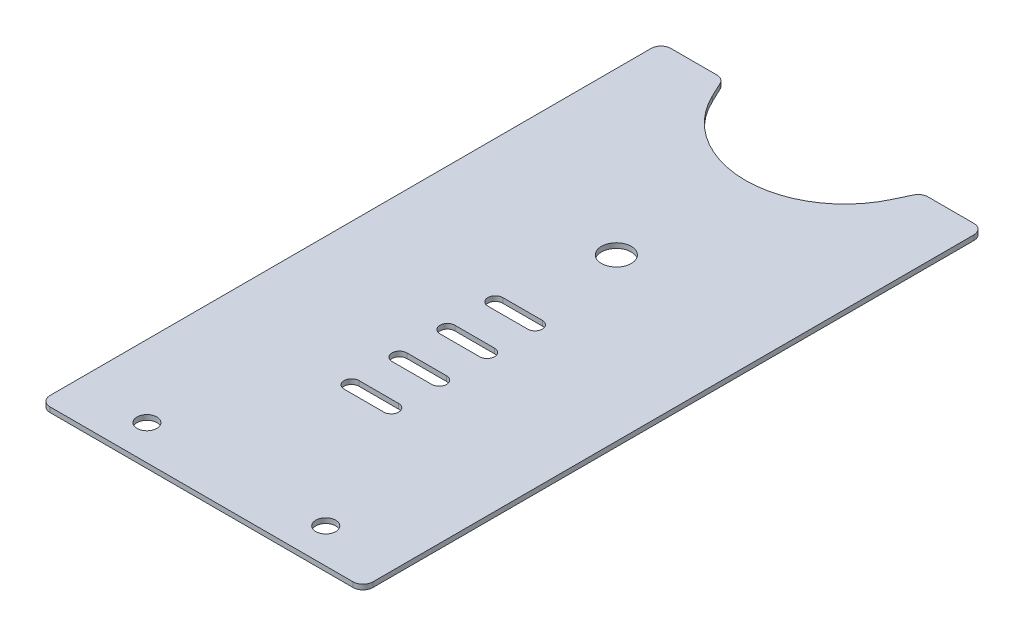
SolidWorks part; units mm, degrees
material "C-玻璃纤维"
ref_plane "前视基准面" through (0, 0, 0) normal (0, 0, 1) x (1, 0, 0)
ref_plane "上视基准面" through (0, 0, 0) normal (0, 1, 0) x (1, 0, 0)
ref_plane "右视基准面" through (0, 0, 0) normal (1, 0, 0) x (0, 0, -1)
sketch "草图1" plane through (0, 0, 0) normal (0, 1, 0) x (1, 0, 0)
  line L0 (0, -55) -> (0, 55) construction
  line L1 (-18.0726, 120.9337) -> (-20, 125)
  line L2 (-20, 125) -> (-32.5, 125)
  line L3 (-32.5, 125) -> (-32.5, 0)
  line L4 (-32.5, 0) -> (32.5, 0)
  line L5 (32.5, 125) -> (32.5, 0)
  line L6 (20, 125) -> (32.5, 125)
  line L7 (18.0726, 120.9337) -> (20, 125)
  line L29 (-4, 34.1906) -> (4, 34.1906) construction
  line L30 (-4, 35.6906) -> (4, 35.6906)
  line L31 (-4, 32.6906) -> (4, 32.6906)
  line L32 (-4, 43.8406) -> (4, 43.8406) construction
  line L33 (-4, 45.3406) -> (4, 45.3406)
  line L34 (-4, 42.3406) -> (4, 42.3406)
  line L35 (-4, 53.4906) -> (4, 53.4906) construction
  line L36 (-4, 54.9906) -> (4, 54.9906)
  line L37 (-4, 51.9906) -> (4, 51.9906)
  line L38 (-4, 63.1406) -> (4, 63.1406) construction
  line L39 (-4, 64.6406) -> (4, 64.6406)
  line L40 (-4, 61.6406) -> (4, 61.6406)
  arc A1 (-18.0726, 120.9337) -> (18.0726, 120.9337) centre (0, 129.5) ccw
  circle A7 centre (-18, 7) radius 2
  circle A8 centre (18, 7) radius 2
  circle A22 centre (0, 83.51) radius 3
  arc A23 (-4, 35.6906) -> (-4, 32.6906) centre (-4, 34.1906) ccw
  arc A24 (4, 32.6906) -> (4, 35.6906) centre (4, 34.1906) ccw
  arc A25 (-4, 45.3406) -> (-4, 42.3406) centre (-4, 43.8406) ccw
  arc A26 (4, 42.3406) -> (4, 45.3406) centre (4, 43.8406) ccw
  arc A27 (-4, 54.9906) -> (-4, 51.9906) centre (-4, 53.4906) ccw
  arc A28 (4, 51.9906) -> (4, 54.9906) centre (4, 53.4906) ccw
  arc A29 (-4, 64.6406) -> (-4, 61.6406) centre (-4, 63.1406) ccw
  arc A30 (4, 61.6406) -> (4, 64.6406) centre (4, 63.1406) ccw
  point P0 (0, 34.1906)
  point P2 (-3.942, 63.1406)
  point P5 (-3.94, 43.8406)
  point P11 (0, 43.8406)
  point P15 (0, 0)
  point P28 (0.05, 83.51)
  point P46 (0, 53.4906)
  point P59 (0, 63.1406)
  dimension "D1" = 7
  dimension "D2" = 12.5
  dimension "D3" = 125
  dimension "D5" = 36
  dimension "D7" = 20
  dimension "D8" = 4
  dimension "D14" = 20.3694
  dimension "D15" = 6
  dimension "D4" = 65
  dimension "D6" = 4.5
  dimension "D9" = 3
  dimension "D10" = 8
  dimension "D11" = 34.1906
  dimension "D13" = 9.65
  dimension "D12" = 4
extrude "凸台-拉伸1" add sketch "草图1" along normal blind 1
fillet "圆角1" radius 2 6 edges at (20, 0.5, -125) (32.5, 0.5, -125) (-20, 0.5, -125) (-32.5, 0.5, 0) (-32.5, 0.5, -125) (32.5, 0.5, 0)
sketch "草图2" plane through (0, 1, 0) normal (0, 1, 0) x (1, 0, 0)
  line L0 (173.3429, 629.6393) -> (1026.6763, 629.6393) construction
  line L1 (0, -55) -> (0, 55) construction
  line L2 (-32.5, 123) -> (-32.5, 2) construction
  line L3 (178.2638, 678.6709) -> (1031.5971, 678.6709) construction
  line L4 (-2.075, 106.1092) -> (-3.3584, 101.7889)
  line L5 (-3.3584, 101.7889) -> (3.3584, 101.7889)
  line L6 (-19.8675, 109.6697) -> (-10.4108, 107.827)
  line L7 (-22.3294, 102.162) -> (-12.7506, 101.6071)
  line L8 (-3.1133, 105.1582) -> (-4.1841, 101.0074)
  line L9 (-4.1841, 101.0074) -> (4.1841, 101.0074)
  line L10 (-3.9935, 81.2053) -> (-5.2494, 75.9189)
  line L11 (-5.2494, 75.9189) -> (-0.0463, 74.6829)
  line L12 (22.3294, 102.162) -> (12.7506, 101.6071)
  line L13 (5.2494, 75.9189) -> (-0.0463, 74.6829)
  line L14 (3.9935, 81.2053) -> (5.2494, 75.9189)
  line L15 (3.1133, 105.1582) -> (4.1841, 101.0074)
  line L16 (19.8675, 109.6697) -> (10.4108, 107.827)
  line L17 (-3.3318, 87.2118) -> (-4.3462, 82.5327)
  line L18 (-4.3462, 82.5327) -> (0.3515, 81.5143)
  line L19 (-2.9266, 92.7641) -> (-4.3552, 87.9155)
  line L20 (-4.3552, 87.9155) -> (-0.0345, 87.0586)
  line L21 (-2.7511, 98.0204) -> (-3.8827, 93.8409)
  line L22 (-3.8827, 93.8409) -> (-0.0463, 93.2555)
  line L23 (3.8827, 93.8409) -> (-0.0463, 93.2555)
  line L24 (2.7511, 98.0204) -> (3.8827, 93.8409)
  line L25 (4.3462, 82.5327) -> (0.3515, 81.5143)
  line L26 (3.3318, 87.2118) -> (4.3462, 82.5327)
  line L27 (4.3552, 87.9155) -> (-0.0345, 87.0586)
  line L28 (2.9266, 92.7641) -> (4.3552, 87.9155)
  line L29 (2.075, 106.1092) -> (3.3584, 101.7889)
  line L30 (-32.5, 100) -> (32.5, 100) construction
  line L32 (32.5, 2) -> (32.5, 123) construction
  line L33 (-2.075, 46.1092) -> (-3.3584, 41.7889)
  line L34 (-21.2653, 125) -> (-30.5, 125) construction
  line L35 (-3.3584, 41.7889) -> (3.3584, 41.7889)
  line L38 (0.5283, 100) -> (-0.4837, 100) construction
  line L43 (-19.8675, 49.6697) -> (-10.4108, 47.827)
  line L45 (-22.3294, 42.162) -> (-12.7506, 41.6071)
  line L60 (-3.1133, 45.1582) -> (-4.1841, 41.0074)
  line L61 (-4.1841, 41.0074) -> (4.1841, 41.0074)
  line L62 (-3.9935, 21.2053) -> (-5.2494, 15.9189)
  line L63 (-5.2494, 15.9189) -> (-0.0463, 14.6829)
  line L64 (22.3294, 42.162) -> (12.7506, 41.6071)
  line L65 (5.2494, 15.9189) -> (-0.0463, 14.6829)
  line L66 (3.9935, 21.2053) -> (5.2494, 15.9189)
  line L67 (3.1133, 45.1582) -> (4.1841, 41.0074)
  line L68 (19.8675, 49.6697) -> (10.4108, 47.827)
  line L69 (-3.3318, 27.2118) -> (-4.3462, 22.5327)
  line L70 (-4.3462, 22.5327) -> (0.3515, 21.5143)
  line L71 (-2.9266, 32.7641) -> (-4.3552, 27.9155)
  line L72 (-4.3552, 27.9155) -> (-0.0345, 27.0586)
  line L73 (-2.7511, 38.0204) -> (-3.8827, 33.8409)
  line L74 (-3.8827, 33.8409) -> (-0.0463, 33.2555)
  line L75 (3.8827, 33.8409) -> (-0.0463, 33.2555)
  line L76 (2.7511, 38.0204) -> (3.8827, 33.8409)
  line L77 (4.3462, 22.5327) -> (0.3515, 21.5143)
  line L78 (3.3318, 27.2118) -> (4.3462, 22.5327)
  line L79 (4.3552, 27.9155) -> (-0.0345, 27.0586)
  line L80 (2.9266, 32.7641) -> (4.3552, 27.9155)
  line L81 (2.075, 46.1092) -> (3.3584, 41.7889)
  spline S0 degree 3 poles (-16.5617, 116.7497) (-9.7804, 114.7297) (-9.7818, 114.8748) (-2.075, 114.348) knots 0 0 0 0 1 1 1 1
  spline S1 degree 3 poles (-2.075, 114.348) (-0.8509, 119.3678) (-0.3777, 81.7523) (1.5803, 116.7571) (2.075, 114.348) knots 0 0 0 0 0.430189 1 1 1 1
  spline S2 degree 3 poles (-16.5617, 116.7497) (-16.4279, 113.773) (-14.3476, 111.5589) (-11.6385, 111.1576) knots 0 0 0 0 1 1 1 1
  spline S3 degree 3 poles (-11.6385, 111.1576) (-11.3827, 108.4756) (-8.8629, 107.6259) (-6.7601, 107.827) knots 0 0 0 0 1 1 1 1
  spline S4 degree 3 poles (-6.7601, 107.827) (-6.04, 106.3521) (-5.0028, 105.2891) (-2.075, 106.1092) knots 0 0 0 0 1 1 1 1
  spline S5 degree 3 poles (6.7601, 107.827) (6.04, 106.3521) (5.0028, 105.2891) (2.075, 106.1092) knots 0 0 0 0 1 1 1 1
  spline S6 degree 3 poles (11.6385, 111.1576) (11.3827, 108.4756) (8.8629, 107.6259) (6.7601, 107.827) knots 0 0 0 0 1 1 1 1
  spline S7 degree 3 poles (16.5617, 116.7497) (16.4279, 113.773) (14.3476, 111.5589) (11.6385, 111.1576) knots 0 0 0 0 1 1 1 1
  spline S8 degree 3 poles (16.5617, 116.7497) (9.7804, 114.7297) (9.7818, 114.8748) (2.075, 114.348) knots 0 0 0 0 1 1 1 1
  spline S9 degree 3 poles (-19.8675, 109.6697) (-17.8911, 104.7559) (-10.8375, 98.5637) (-2.7511, 98.0204) knots 0 0 0 0 1 1 1 1
  spline S10 degree 3 poles (-22.3294, 102.162) (-18.2675, 95.7927) (-11.2844, 93.146) (-2.9266, 92.7641) knots 0 0 0 0 1 1 1 1
  spline S11 degree 3 poles (-25.3767, 95.6389) (-23.0081, 91.1831) (-15.2931, 88.1635) (-3.3318, 87.2118) knots 0 0 0 0 1 1 1 1
  spline S12 degree 3 poles (-27.9693, 89.3013) (-24.3699, 84.7234) (-28.8455, 85.1687) (-3.9935, 81.2053) knots 0 0 0 0 1 1 1 1
  spline S13 degree 3 poles (-27.9693, 89.3013) (-24.7439, 88.2361) (-23.7856, 87.9656) (-11.4548, 88.2965) knots 0 0 0 0 1 1 1 1
  spline S14 degree 3 poles (-25.3767, 95.6389) (-22.4978, 95.0398) (-19.9992, 94.9933) (-14.7163, 95.4427) knots 0 0 0 0 1 1 1 1
  spline S15 degree 3 poles (-10.4108, 107.827) (-9.3209, 107.1792) (-9.1946, 107.0534) (-7.2518, 107.0534) knots 0 0 0 0 1 1 1 1
  spline S16 degree 3 poles (-7.2518, 107.0534) (-6.1832, 105.4019) (-5.1373, 104.9889) (-3.1133, 105.1582) knots 0 0 0 0 1 1 1 1
  spline S17 degree 3 poles (25.3767, 95.6389) (22.4978, 95.0398) (19.9992, 94.9933) (14.7163, 95.4427) knots 0 0 0 0 1 1 1 1
  spline S18 degree 3 poles (27.9693, 89.3013) (24.7439, 88.2361) (23.7856, 87.9656) (11.4548, 88.2965) knots 0 0 0 0 1 1 1 1
  spline S19 degree 3 poles (27.9693, 89.3013) (24.3699, 84.7234) (28.8455, 85.1687) (3.9935, 81.2053) knots 0 0 0 0 1 1 1 1
  spline S20 degree 3 poles (25.3767, 95.6389) (23.0081, 91.1831) (15.2931, 88.1635) (3.3318, 87.2118) knots 0 0 0 0 1 1 1 1
  spline S21 degree 3 poles (22.3294, 102.162) (18.2675, 95.7927) (11.2844, 93.146) (2.9266, 92.7641) knots 0 0 0 0 1 1 1 1
  spline S22 degree 3 poles (19.8675, 109.6697) (17.8911, 104.7559) (10.8375, 98.5637) (2.7511, 98.0204) knots 0 0 0 0 1 1 1 1
  spline S23 degree 3 poles (7.2518, 107.0534) (6.1832, 105.4019) (5.1373, 104.9889) (3.1133, 105.1582) knots 0 0 0 0 1 1 1 1
  spline S24 degree 3 poles (10.4108, 107.827) (9.3209, 107.1792) (9.1946, 107.0534) (7.2518, 107.0534) knots 0 0 0 0 1 1 1 1
  spline S25 degree 3 poles (-16.5617, 56.7497) (-9.7804, 54.7297) (-9.7818, 54.8751) (-2.075, 54.3482) knots 0 0 0 0 1 1 1 1
  spline S26 degree 3 poles (-2.075, 54.3482) (-0.8509, 59.368) (-0.3777, 60.539) (1.5803, 59.5765) (2.075, 54.3482) knots 0 0 0 0 0.430189 1 1 1 1
  spline S27 degree 3 poles (-16.5617, 56.7497) (-16.4279, 53.773) (-14.3476, 51.5589) (-11.6385, 51.1576) knots 0 0 0 0 1 1 1 1
  spline S28 degree 3 poles (-11.6385, 51.1576) (-11.3827, 48.4756) (-8.8629, 47.6259) (-6.7601, 47.827) knots 0 0 0 0 1 1 1 1
  spline S29 degree 3 poles (-6.7601, 47.827) (-6.04, 46.3521) (-5.0028, 45.2891) (-2.075, 46.1092) knots 0 0 0 0 1 1 1 1
  spline S30 degree 3 poles (6.7601, 47.827) (6.04, 46.3521) (5.0028, 45.2891) (2.075, 46.1092) knots 0 0 0 0 1 1 1 1
  spline S31 degree 3 poles (11.6385, 51.1576) (11.3827, 48.4756) (8.8629, 47.6259) (6.7601, 47.827) knots 0 0 0 0 1 1 1 1
  spline S32 degree 3 poles (16.5617, 56.7497) (16.4279, 53.773) (14.3476, 51.5589) (11.6385, 51.1576) knots 0 0 0 0 1 1 1 1
  spline S33 degree 3 poles (16.5617, 56.7497) (9.7804, 54.7297) (9.7818, 54.8751) (2.075, 54.3482) knots 0 0 0 0 1 1 1 1
  spline S34 degree 3 poles (-19.8675, 49.6697) (-17.8911, 44.7559) (-10.8375, 38.5637) (-2.7511, 38.0204) knots 0 0 0 0 1 1 1 1
  spline S35 degree 3 poles (-22.3294, 42.162) (-18.2675, 35.7927) (-11.2844, 33.146) (-2.9266, 32.7641) knots 0 0 0 0 1 1 1 1
  spline S36 degree 3 poles (-25.3767, 35.6389) (-23.0081, 31.1831) (-15.2931, 28.1635) (-3.3318, 27.2118) knots 0 0 0 0 1 1 1 1
  spline S37 degree 3 poles (-27.9693, 29.3013) (-24.3699, 24.7234) (-28.8455, 25.1687) (-3.9935, 21.2053) knots 0 0 0 0 1 1 1 1
  spline S38 degree 3 poles (-27.9693, 29.3013) (-24.7439, 28.2361) (-23.7856, 27.9656) (-11.4548, 28.2965) knots 0 0 0 0 1 1 1 1
  spline S39 degree 3 poles (-25.3767, 35.6389) (-22.4978, 35.0398) (-19.9992, 34.9933) (-14.7163, 35.4427) knots 0 0 0 0 1 1 1 1
  spline S40 degree 3 poles (-10.4108, 47.827) (-9.3209, 47.1792) (-9.1946, 47.0534) (-7.2518, 47.0534) knots 0 0 0 0 1 1 1 1
  spline S41 degree 3 poles (-7.2518, 47.0534) (-6.1832, 45.4019) (-5.1373, 44.9889) (-3.1133, 45.1582) knots 0 0 0 0 1 1 1 1
  spline S42 degree 3 poles (25.3767, 35.6389) (22.4978, 35.0398) (19.9992, 34.9933) (14.7163, 35.4427) knots 0 0 0 0 1 1 1 1
  spline S43 degree 3 poles (27.9693, 29.3013) (24.7439, 28.2361) (23.7856, 27.9656) (11.4548, 28.2965) knots 0 0 0 0 1 1 1 1
  spline S44 degree 3 poles (27.9693, 29.3013) (24.3699, 24.7234) (28.8455, 25.1687) (3.9935, 21.2053) knots 0 0 0 0 1 1 1 1
  spline S45 degree 3 poles (25.3767, 35.6389) (23.0081, 31.1831) (15.2931, 28.1635) (3.3318, 27.2118) knots 0 0 0 0 1 1 1 1
  spline S46 degree 3 poles (22.3294, 42.162) (18.2675, 35.7927) (11.2844, 33.146) (2.9266, 32.7641) knots 0 0 0 0 1 1 1 1
  spline S47 degree 3 poles (19.8675, 49.6697) (17.8911, 44.7559) (10.8375, 38.5637) (2.7511, 38.0204) knots 0 0 0 0 1 1 1 1
  spline S48 degree 3 poles (7.2518, 47.0534) (6.1832, 45.4019) (5.1373, 44.9889) (3.1133, 45.1582) knots 0 0 0 0 1 1 1 1
  spline S49 degree 3 poles (10.4108, 47.827) (9.3209, 47.1792) (9.1946, 47.0534) (7.2518, 47.0534) knots 0 0 0 0 1 1 1 1
  dimension "D1" = 25
  dimension "D2" = 2
extrude "切除-拉伸1" [suppressed] cut sketch "草图2" against normal through all contours S7 S8 S1 S0 S2 S3 S4 L4 L5 L29 S5 S6 | L16 S24 S23 L15 L9 L8 S16 S15 L6 S9 L21 L22 L23 L24 S22 | L12 S22 L24 L23 L22 L21 S9 L7 S10 L19 L20 L27 L28 S21 | S17 S21 L28 L27 L20 L19 S10 S14 S11 L17 L18 L25 L26 S20 | S18 S20 L26 L25 L18 L17 S11 S13 S12 L10 L11 L13 L14 S19 | S32 S33 S26 S25 S27 S28 S29 L33 L35 L81 S30 S31 | L68 S49 S48 L67 L61 L60 S41 S40 L43 S34 L73 L74 L75 L76 S47 | L64 S47 L76 L75 L74 L73 S34 L45 S35 L71 L72 L79 L80 S46 | S42 S46 L80 L79 L72 L71 S35 S39 S36 L69 L70 L77 L78 S45 | S43 S45 L78 L77 L70 L69 S36 S38 S37 L62 L63 L65 L66 S44
sketch "草图4" [suppressed] plane through (0, 1, 0) normal (0, 1, 0) x (1, 0, 0)
  line L0 (-3.3318, 87.2118) -> (-4.3462, 82.5327) construction
  line L1 (-4.3462, 82.5327) -> (0.3515, 81.5143) construction
  line L2 (4.3462, 82.5327) -> (0.3515, 81.5143) construction
  line L3 (3.3318, 87.2118) -> (4.3462, 82.5327) construction
  line L4 (4.3552, 87.9155) -> (-0.0345, 87.0586) construction
  line L5 (-4.3552, 87.9155) -> (-0.0345, 87.0586) construction
  line L6 (-2.9266, 92.7641) -> (-4.3552, 87.9155) construction
  line L7 (-3.8827, 93.8409) -> (-0.0463, 93.2555) construction
  line L8 (3.8827, 93.8409) -> (-0.0463, 93.2555) construction
  line L9 (2.7511, 98.0204) -> (3.8827, 93.8409) construction
  line L10 (-2.7511, 98.0204) -> (-3.8827, 93.8409) construction
  line L11 (-3.3318, 87.2118) -> (-4.3462, 82.5327)
  line L12 (-4.3462, 82.5327) -> (0.3515, 81.5143)
  line L13 (4.3462, 82.5327) -> (0.3515, 81.5143)
  line L14 (3.3318, 87.2118) -> (4.3462, 82.5327)
  line L15 (4.3552, 87.9155) -> (-0.0345, 87.0586)
  line L16 (-4.3552, 87.9155) -> (-0.0345, 87.0586)
  line L17 (-2.9266, 92.7641) -> (-4.3552, 87.9155)
  line L18 (-3.8827, 93.8409) -> (-0.0463, 93.2555)
  line L19 (3.8827, 93.8409) -> (-0.0463, 93.2555)
  line L20 (2.7511, 98.0204) -> (3.8827, 93.8409)
  line L21 (-2.7511, 98.0204) -> (-3.8827, 93.8409)
  line L22 (3.1133, 105.1582) -> (4.1841, 101.0074) construction
  line L23 (-4.1841, 101.0074) -> (4.1841, 101.0074) construction
  line L24 (-3.1133, 105.1582) -> (-4.1841, 101.0074) construction
  line L25 (3.1133, 105.1582) -> (4.1841, 101.0074)
  line L26 (-4.1841, 101.0074) -> (4.1841, 101.0074)
  line L27 (-3.1133, 105.1582) -> (-4.1841, 101.0074)
  line L28 (2.9266, 92.7641) -> (4.3552, 87.9155) construction
  line L29 (2.9266, 92.7641) -> (4.3552, 87.9155)
  line L30 (0, -0.55) -> (0, 0.55) construction
  line L31 (3.9935, 81.2053) -> (5.2494, 75.9189) construction
  line L32 (5.2494, 75.9189) -> (-0.0463, 74.6829) construction
  line L33 (-5.2494, 75.9189) -> (-0.0463, 74.6829) construction
  line L34 (-3.9935, 81.2053) -> (-5.2494, 75.9189) construction
  line L35 (3.9935, 81.2053) -> (5.2494, 75.9189)
  line L36 (5.2494, 75.9189) -> (-0.0463, 74.6829)
  line L37 (-5.2494, 75.9189) -> (-0.0463, 74.6829)
  line L38 (-3.9935, 81.2053) -> (-5.2494, 75.9189)
  line L51 (-3.3318, 27.2118) -> (-4.3462, 22.5327)
  line L52 (-4.3462, 22.5327) -> (0.3515, 21.5143)
  line L53 (4.3462, 22.5327) -> (0.3515, 21.5143)
  line L54 (3.3318, 27.2118) -> (4.3462, 22.5327)
  line L55 (4.3552, 27.9155) -> (-0.0345, 27.0586)
  line L56 (-4.3552, 27.9155) -> (-0.0345, 27.0586)
  line L57 (-2.9266, 32.7641) -> (-4.3552, 27.9155)
  line L58 (-3.8827, 33.8409) -> (-0.0463, 33.2555)
  line L59 (3.8827, 33.8409) -> (-0.0463, 33.2555)
  line L60 (2.7511, 38.0204) -> (3.8827, 33.8409)
  line L61 (-2.7511, 38.0204) -> (-3.8827, 33.8409)
  line L62 (3.1133, 45.1582) -> (4.1841, 41.0074)
  line L66 (-4.1841, 41.0074) -> (4.1841, 41.0074)
  line L67 (-3.1133, 45.1582) -> (-4.1841, 41.0074)
  line L68 (2.9266, 32.7641) -> (4.3552, 27.9155)
  line L72 (3.9935, 21.2053) -> (5.2494, 15.9189)
  line L73 (5.2494, 15.9189) -> (-0.0463, 14.6829)
  line L74 (-5.2494, 15.9189) -> (-0.0463, 14.6829)
  line L75 (-3.9935, 21.2053) -> (-5.2494, 15.9189)
  spline S0 degree 3 poles (2958.1902, -22.8193) (-2897.5097, 867.7056) (2029.1971, -1562.4521) (46.0324, 2846.0976) knots -10.523229 -10.523229 -10.523229 -10.523229 14.71724 14.71724 14.71724 14.71724 only from (-25.3767, 95.6389) to (-3.3318, 87.2118) construction
  spline S1 degree 3 poles (-2958.1902, -22.8193) (2897.5097, 867.7056) (-2029.1971, -1562.4521) (-46.0324, 2846.0976) knots -10.523229 -10.523229 -10.523229 -10.523229 14.71724 14.71724 14.71724 14.71724 only from (25.3767, 95.6389) to (3.3318, 87.2118) construction
  spline S2 degree 3 poles (-1870.8103, 2423.0691) (2392.6968, -2248.3866) (-2609.3286, 2331.1604) (2264.3202, -1878.0362) knots -9.308051 -9.308051 -9.308051 -9.308051 13.823001 13.823001 13.823001 13.823001 only from (22.3294, 102.162) to (2.9266, 92.7641) construction
  spline S3 degree 3 poles (1870.8103, 2423.0691) (-2392.6968, -2248.3866) (2609.3286, 2331.1604) (-2264.3202, -1878.0362) knots -9.308051 -9.308051 -9.308051 -9.308051 13.823001 13.823001 13.823001 13.823001 only from (-22.3294, 102.162) to (-2.9266, 92.7641) construction
  spline S4 degree 3 poles (-1930.1034, -2164.3039) (1779.328, 2697.2184) (-1404.6938, -2682.4546) (922.6244, 2943.5918) knots -6.818673 -6.818673 -6.818673 -6.818673 7.710574 7.710574 7.710574 7.710574 only from (19.8675, 109.6697) to (2.7511, 98.0204) construction
  spline S5 degree 3 poles (1930.1034, -2164.3039) (-1779.328, 2697.2184) (1404.6938, -2682.4546) (-922.6244, 2943.5918) knots -6.818673 -6.818673 -6.818673 -6.818673 7.710574 7.710574 7.710574 7.710574 only from (-19.8675, 109.6697) to (-2.7511, 98.0204) construction
  spline S6 degree 3 poles (-25.3767, 95.6389) (-23.0081, 91.1831) (-15.2931, 88.1635) (-3.3318, 87.2118) knots 0 0 0 0 1 1 1 1
  spline S7 degree 3 poles (25.3767, 95.6389) (23.0081, 91.1831) (15.2931, 88.1635) (3.3318, 87.2118) knots 0 0 0 0 1 1 1 1
  spline S8 degree 3 poles (22.3294, 102.162) (18.2675, 95.7927) (11.2844, 93.146) (2.9266, 92.7641) knots 0 0 0 0 1 1 1 1
  spline S9 degree 3 poles (-22.3294, 102.162) (-18.2675, 95.7927) (-11.2844, 93.146) (-2.9266, 92.7641) knots 0 0 0 0 1 1 1 1
  spline S10 degree 3 poles (19.8675, 109.6697) (17.8911, 104.7559) (10.8375, 98.5637) (2.7511, 98.0204) knots 0 0 0 0 1 1 1 1
  spline S11 degree 3 poles (-19.8675, 109.6697) (-17.8911, 104.7559) (-10.8375, 98.5637) (-2.7511, 98.0204) knots 0 0 0 0 1 1 1 1
  spline S12 degree 3 poles (-25.3767, 35.6389) (-23.0081, 31.1831) (-15.2931, 28.1635) (-3.3318, 27.2118) knots 0 0 0 0 1 1 1 1
  spline S13 degree 3 poles (2177.8491, 2172.0535) (-2293.3828, -1628.2892) (2503.6874, 1529.3711) (-2766.913, -1032.8577) knots -12.840031 -12.840031 -12.840031 -12.840031 13.994627 13.994627 13.994627 13.994627 only from (7.2518, 107.0534) to (3.1133, 105.1582) construction
  spline S14 degree 3 poles (-2177.8491, 2172.0535) (2293.3828, -1628.2892) (-2503.6874, 1529.3711) (2766.913, -1032.8577) knots -12.840031 -12.840031 -12.840031 -12.840031 13.994627 13.994627 13.994627 13.994627 only from (-7.2518, 107.0534) to (-3.1133, 105.1582) construction
  spline S15 degree 3 poles (25.3767, 35.6389) (23.0081, 31.1831) (15.2931, 28.1635) (3.3318, 27.2118) knots 0 0 0 0 1 1 1 1
  spline S16 degree 3 poles (22.3294, 42.162) (18.2675, 35.7927) (11.2844, 33.146) (2.9266, 32.7641) knots 0 0 0 0 1 1 1 1
  spline S17 degree 3 poles (7.0838, 106.8037) (6.0708, 105.3602) (5.0311, 104.9978) (3.1133, 105.1582) knots 0.052433 0.052433 0.052433 0.052433 1 1 1 1
  spline S18 degree 3 poles (-7.0838, 106.8037) (-6.0708, 105.3602) (-5.0311, 104.9978) (-3.1133, 105.1582) knots 0.052433 0.052433 0.052433 0.052433 1 1 1 1
  spline S19 degree 3 poles (17.5607, 116.7048) (17.4898, 115.1277) (16.9369, 113.7052) (15.1481, 111.4819) (13.9142, 110.6802) (12.5074, 110.3151) knots 0 0 0 0 0.5 0.5 1 1 1 1
  spline S20 degree 3 poles (12.5074, 110.3151) (12.3338, 109.6171) (12.0103, 109.0086) (11.167, 108.0302) (10.653, 107.6607) (9.5591, 107.1288) (8.978, 106.9637) (7.9559, 106.8098) (7.5152, 106.7875) (7.0838, 106.8037) knots 0 0 0 0 0.25 0.25 0.5 0.5 0.75 0.75 0.938518 0.938518 0.938518 0.938518
  spline S21 degree 3 poles (3758.6205, -1193.6001) (112.8687, 340.2932) (-28.5209, 128.1637) (-11.167, 108.0302) (-10.653, 107.6607) (-9.5591, 107.1288) (-8.978, 106.9637) (23.0367, 102.1412) (61.3073, 322.4606) (-3752.8197, -1283.6022) knots -9.789405 -9.789405 -9.789405 -9.789405 0.25 0.25 0.5 0.5 0.75 0.75 14.236667 14.236667 14.236667 14.236667 only from (-12.5074, 110.3151) to (-6.6649, 106.8316)
  spline S22 degree 3 poles (2885.8566, 998.7557) (-2834.7943, -679.3502) (2920.7371, 752.994) (-2933.6622, -525.7806) knots -4.016596 -4.016596 -4.016596 -4.016596 4.497714 4.497714 4.497714 4.497714 only from (27.9693, 89.3013) to (3.9935, 81.2053) construction
  spline S23 degree 3 poles (-2885.8566, 998.7557) (2834.7943, -679.3502) (-2920.7371, 752.994) (2933.6622, -525.7806) knots -4.016596 -4.016596 -4.016596 -4.016596 4.497714 4.497714 4.497714 4.497714 only from (-27.9693, 89.3013) to (-3.9935, 81.2053) construction
  spline S24 degree 3 poles (3295.8981, -2094.8102) (178.7414, 392.5298) (-39.8722, 142.2112) (8.1813, 82.486) (281.4732, 279.7915) (-2508.4057, 3216.0094) knots -12.821471 -12.821471 -12.821471 -12.821471 0.5 0.5 14.041801 14.041801 14.041801 14.041801 only from (-17.5607, 116.7048) to (-12.5074, 110.3151)
  spline S25 degree 3 poles (-12.5074, 110.3151) (-12.3338, 109.6171) (-12.0103, 109.0086) (-11.167, 108.0302) (-10.653, 107.6607) (-9.5591, 107.1288) (-8.978, 106.9637) (-7.9559, 106.8098) (-7.5152, 106.7875) (-7.0838, 106.8037) knots 0 0 0 0 0.25 0.25 0.5 0.5 0.75 0.75 0.938518 0.938518 0.938518 0.938518
  spline S26 degree 3 poles (-17.5607, 116.7048) (-17.4898, 115.1277) (-16.9369, 113.7052) (-15.1481, 111.4819) (-13.9142, 110.6802) (-12.5074, 110.3151) knots 0 0 0 0 0.5 0.5 1 1 1 1
  spline S27 degree 3 poles (-22.3294, 42.162) (-18.2675, 35.7927) (-11.2844, 33.146) (-2.9266, 32.7641) knots 0 0 0 0 1 1 1 1
  spline S28 degree 3 poles (27.9693, 89.3013) (24.3699, 84.7234) (28.8455, 85.1687) (3.9935, 81.2053) knots 0 0 0 0 1 1 1 1
  spline S29 degree 3 poles (-27.9693, 89.3013) (-24.3699, 84.7234) (-28.8455, 85.1687) (-3.9935, 81.2053) knots 0 0 0 0 1 1 1 1
  spline S36 degree 3 poles (19.8675, 49.6697) (17.8911, 44.7559) (10.8375, 38.5637) (2.7511, 38.0204) knots 0 0 0 0 1 1 1 1
  spline S37 degree 3 poles (-19.8675, 49.6697) (-17.8911, 44.7559) (-10.8375, 38.5637) (-2.7511, 38.0204) knots 0 0 0 0 1 1 1 1
  spline S38 degree 3 poles (7.0838, 46.8037) (6.0708, 45.3602) (5.0311, 44.9978) (3.1133, 45.1582) knots 0.052433 0.052433 0.052433 0.052433 1 1 1 1
  spline S39 degree 3 poles (-7.0838, 46.8037) (-6.0708, 45.3602) (-5.0311, 44.9978) (-3.1133, 45.1582) knots 0.052433 0.052433 0.052433 0.052433 1 1 1 1
  spline S40 degree 3 poles (17.5607, 56.7048) (17.4898, 55.1277) (16.9369, 53.7052) (15.1481, 51.4819) (13.9142, 50.6802) (12.5074, 50.3151) knots 0 0 0 0 0.5 0.5 1 1 1 1
  spline S41 degree 3 poles (12.5074, 50.3151) (12.3338, 49.6171) (12.0103, 49.0086) (11.167, 48.0302) (10.653, 47.6607) (9.5591, 47.1288) (8.978, 46.9637) (7.9559, 46.8098) (7.5152, 46.7875) (7.0838, 46.8037) knots 0 0 0 0 0.25 0.25 0.5 0.5 0.75 0.75 0.938518 0.938518 0.938518 0.938518
  spline S44 degree 3 poles (-12.5074, 50.3151) (-12.3338, 49.6171) (-12.0103, 49.0086) (-11.167, 48.0302) (-10.653, 47.6607) (-9.5591, 47.1288) (-8.978, 46.9637) (-7.9559, 46.8098) (-7.5152, 46.7875) (-7.0838, 46.8037) knots 0 0 0 0 0.25 0.25 0.5 0.5 0.75 0.75 0.938518 0.938518 0.938518 0.938518
  spline S45 degree 3 poles (-17.5607, 56.7048) (-17.4898, 55.1277) (-16.9369, 53.7052) (-15.1481, 51.4819) (-13.9142, 50.6802) (-12.5074, 50.3151) knots 0 0 0 0 0.5 0.5 1 1 1 1
  spline S46 degree 3 poles (27.9693, 29.3013) (24.3699, 24.7234) (28.8455, 25.1687) (3.9935, 21.2053) knots 0 0 0 0 1 1 1 1
  spline S47 degree 3 poles (-27.9693, 29.3013) (-24.3699, 24.7234) (-28.8455, 25.1687) (-3.9935, 21.2053) knots 0 0 0 0 1 1 1 1
  dimension "D3" = 60
  dimension "D1" = 1
  dimension "D2" = 2
extrude "拉伸-薄壁1" [suppressed] add sketch "草图4" against normal up to surface (1 mm away) thin thin type two direction wall 1 second wall 0.75
